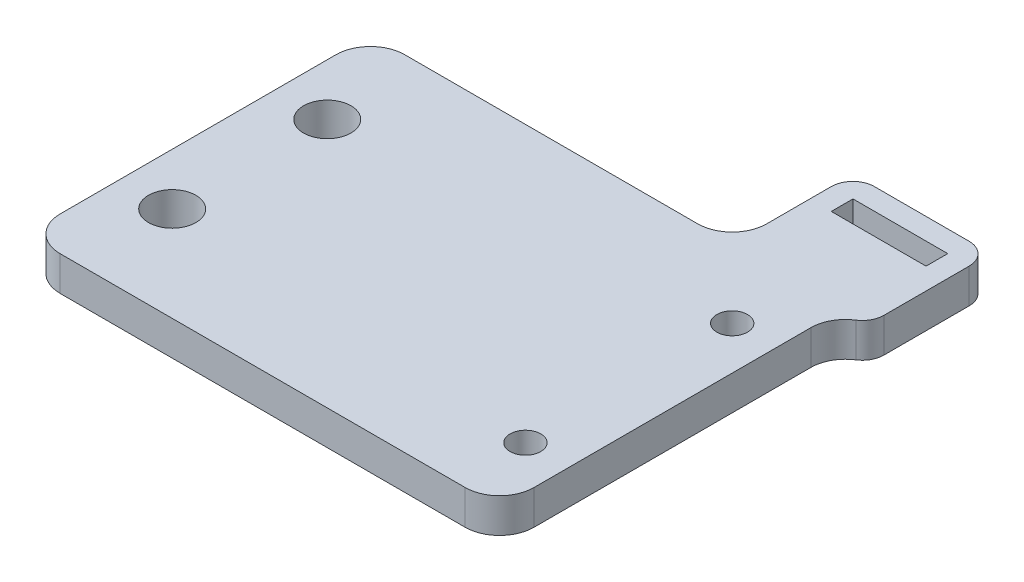
SolidWorks part; units mm, degrees
ref_plane "Front" through (0, 0, 0) normal (0, 0, 1) x (1, 0, 0)
ref_plane "Top" through (0, 0, 0) normal (0, 1, 0) x (1, 0, 0)
ref_plane "Right" through (0, 0, 0) normal (1, 0, 0) x (0, 0, -1)
sketch "Sketch1" plane through (0, 0, 0) normal (0, 1, 0) x (1, 0, 0)
  line L1 (0, 0) -> (34.925, 0)
  line L2 (0, 0) -> (0, 25.4)
  line L3 (0, 25.4) -> (34.925, 25.4)
  line L4 (34.925, 0) -> (34.925, 25.4)
  dimension "D1" = 25.4
  dimension "D2" = 34.925
extrude "Boss-Extrude1" add sketch "Sketch1" along normal blind 2.54
sketch "Sketch2" plane through (0, 2.54, 0) normal (0, 1, 0) x (1, 0, 0)
  line L0 (0, 12.7) -> (34.925, 12.7) construction
  line L1 (0, 25.4) -> (0, 0) construction
  line L2 (34.925, 0) -> (34.925, 25.4) construction
  circle A0 centre (3.81, 18.415) radius 1.7462
  circle A1 centre (3.81, 6.985) radius 1.7463
  dimension "D1" = 3.4925
  dimension "D2" = 5.715
  dimension "D3" = 3.81
extrude "Cut-Extrude3" cut sketch "Sketch2" along normal through all and the other way through all
sketch "Sketch5" plane through (0, 2.54, 0) normal (0, 1, 0) x (1, 0, 0)
  line L0 (0, 12.7) -> (34.925, 12.7) construction
  line L1 (0, 25.4) -> (0, 0) construction
  line L2 (34.925, 0) -> (34.925, 25.4) construction
  line L3 (34.925, 25.4) -> (0, 25.4) construction
  circle A0 centre (31.75, 20.32) radius 1.1303
  circle A1 centre (31.75, 5.08) radius 1.1303
  dimension "D1" = 2.2606
  dimension "D2" = 5.08
  dimension "D3" = 3.175
extrude "Cut-Extrude4" cut sketch "Sketch5" against normal through all
sketch "Sketch6" plane through (0, 2.54, 0) normal (0, 1, 0) x (1, 0, 0)
  line L0 (31.75, 20.32) -> (31.75, 5.08) construction
  line L1 (31.75, 20.32) -> (31.75, 38.7587) construction
  line L2 (34.925, 25.4) -> (0, 25.4) construction
  line L3 (36.83, 34.29) -> (26.67, 34.29)
  line L4 (36.83, 34.29) -> (36.83, 25.4)
  line L5 (36.83, 25.4) -> (26.67, 25.4)
  line L6 (26.67, 34.29) -> (26.67, 25.4)
  line L7 (36.83, 34.29) -> (26.67, 25.4) construction
  line L8 (36.83, 25.4) -> (26.67, 34.29) construction
  point P5 (31.75, 29.845)
  point P12 (31.75, 12.7)
  dimension "D1" = 21.59
  dimension "D2" = 10.16
extrude "Boss-Extrude2" add sketch "Sketch6" against normal blind 2.54
sketch "Sketch7" plane through (0, 2.54, 0) normal (0, 1, 0) x (1, 0, 0)
  line L0 (31.75, 5.08) -> (31.75, 18.1072) construction
  line L1 (31.75, 18.1072) -> (31.75, 34.29) construction
  line L2 (36.83, 34.29) -> (26.67, 34.29) construction
  line L4 (28.2575, 32.7137) -> (35.2425, 32.7137)
  line L5 (28.2575, 32.7137) -> (28.2575, 31.1135)
  line L6 (28.2575, 31.1135) -> (35.2425, 31.1135)
  line L7 (35.2425, 32.7137) -> (35.2425, 31.1135)
  line L8 (28.2575, 32.7137) -> (35.2425, 31.1135) construction
  line L9 (28.2575, 31.1135) -> (35.2425, 32.7137) construction
  point P3 (31.75, 31.9136)
  point P11 (31.75, 11.5936)
  dimension "D1" = 20.32
  dimension "D2" = 1.6002
  dimension "D3" = 6.985
extrude "Cut-Extrude5" cut sketch "Sketch7" against normal through all
fillet "Fillet1" radius 2.54 2 edges at (34.925, 1.27, -25.4) (26.67, 1.27, -25.4)
fillet "Fillet2" radius 1.5875 3 edges at (36.83, 1.27, -34.29) (26.67, 1.27, -34.29) (36.83, 1.27, -25.4)
fillet "Fillet3" radius 2.54 3 edges at (0, 1.27, 0) (0, 1.27, -25.4) (34.925, 1.27, 0)
